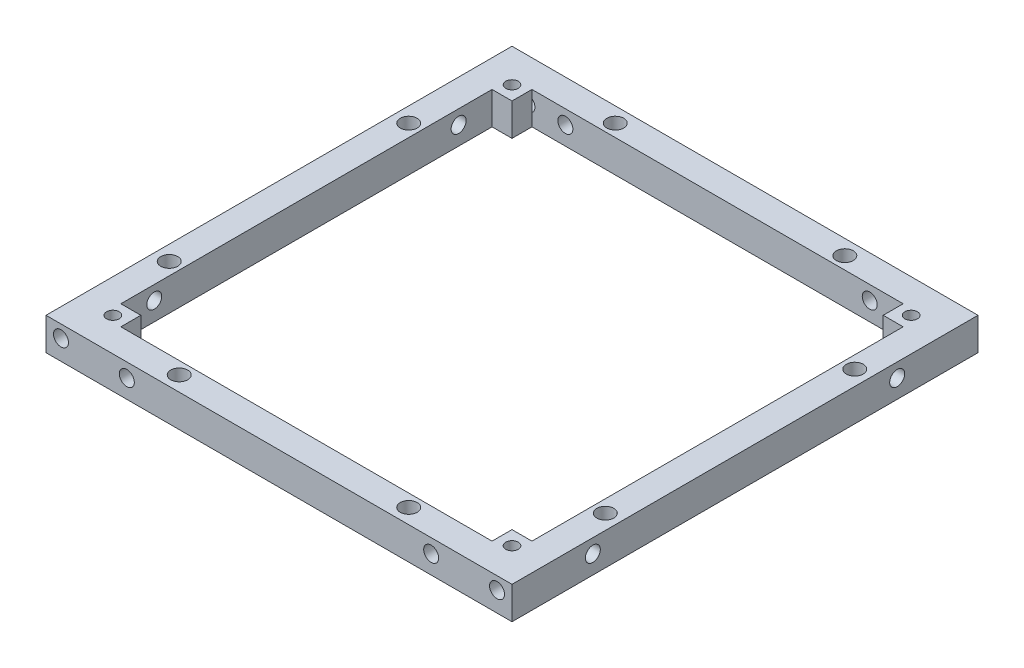
SolidWorks part; units mm, degrees
material "Aluminum"
ref_plane "Front Plane" through (0, 0, 0) normal (0, 0, 1) x (1, 0, 0)
ref_plane "Top Plane" through (0, 0, 0) normal (0, 1, 0) x (1, 0, 0)
ref_plane "Right Plane" through (0, 0, 0) normal (1, 0, 0) x (0, 0, -1)
sketch "Sketch1" plane through (0, 0, 0) normal (0, 1, 0) x (1, 0, 0)
  line L1 (46.7, -46.7) -> (-46.7, -46.7)
  line L2 (46.7, -46.7) -> (46.7, 46.7)
  line L3 (46.7, 46.7) -> (-46.7, 46.7)
  line L4 (-46.7, -46.7) -> (-46.7, 46.7)
  line L5 (46.7, -46.7) -> (-46.7, 46.7) construction
  line L6 (46.7, 46.7) -> (-46.7, -46.7) construction
  line L7 (38.7, -38.7) -> (-38.7, -38.7)
  line L8 (38.7, -38.7) -> (38.7, 38.7)
  line L9 (38.7, 38.7) -> (-38.7, 38.7)
  line L10 (-38.7, -38.7) -> (-38.7, 38.7)
  line L11 (38.7, -38.7) -> (-38.7, 38.7) construction
  line L12 (38.7, 38.7) -> (-38.7, -38.7) construction
  point P0 (0, 0)
  point P6 (0, 0)
  dimension "D1" = 93.4
  dimension "D2" = 93.4
  dimension "D3" = 8
extrude "Boss-Extrude1" add sketch "Sketch1" along normal blind 8
hole_wizard "Ø3.0 (3) Diameter Hole6" positions "Sketch8" profile "Sketch7" hole size "Ø3.0" standard "ANSI Metric"
sketch "Sketch8" plane through (0, 0, 46.7) normal (0, 0, 1) x (1, 0, 0)
  line L0 (46.7, 8) -> (46.7, 0) construction
  line L1 (-46.7, 8) -> (-46.7, 0) construction
  line L2 (-46.7, 0) -> (46.7, 0) construction
  point P0 (43.7, 4)
  point P2 (-43.7, 4)
  dimension "D1" = 3
  dimension "D2" = 3
  dimension "D3" = 4
  dimension "D4" = 4
sketch "Sketch7" plane through (43.7, 4, 46.7) normal (1, 0, 0) x (0, -1, 0)
  line L0 (0, 0) -> (0, 7.5)
  line L1 (0, 7.5) -> (1.5, 7.5)
  line L2 (1.5, 7.5) -> (1.5, 0)
  line L5 (1.5, 0) -> (0, 0)
  line L10 (0, 7.5) -> (-1.5, 7.5) construction
  line L11 (0, -6.35) -> (0, 107.95) construction
  dimension "Hole Dia." = 3
  dimension "Hole Depth" = 7.5
  dimension "Drill Angle" = 180
hole_wizard "Ø3.0 (3) Diameter Hole3" positions "Sketch10" profile "Sketch9" hole size "Ø3.0" standard "ANSI Metric"
sketch "Sketch10" plane through (0, 0, -46.7) normal (0, 0, -1) x (-1, 0, 0)
  line L0 (-46.7, 8) -> (-46.7, 0) construction
  line L1 (46.7, 8) -> (46.7, 0) construction
  line L2 (-46.7, 0) -> (46.7, 0) construction
  point P0 (-43.7, 4)
  point P2 (43.7, 4)
  dimension "D1" = 3
  dimension "D2" = 3
  dimension "D3" = 4
  dimension "D4" = 4
sketch "Sketch9" plane through (43.7, 4, -46.7) normal (1, 0, 0) x (0, 1, 0)
  line L0 (0, 0) -> (0, 7.5)
  line L1 (0, 7.5) -> (1.5, 7.5)
  line L2 (1.5, 7.5) -> (1.5, 0)
  line L5 (1.5, 0) -> (0, 0)
  line L10 (0, 7.5) -> (-1.5, 7.5) construction
  line L11 (0, -6.35) -> (0, 107.95) construction
  dimension "Hole Dia." = 3
  dimension "Hole Depth" = 7.5
  dimension "Drill Angle" = 180
sketch "Sketch27" plane through (0, 8, 0) normal (0, 1, 0) x (1, 0, 0)
  line L0 (-38.7, 38.7) -> (-38.7, -38.7) construction
  line L1 (39.7, -39.7) -> (-39.7, -39.7)
  line L2 (39.7, -39.7) -> (39.7, 39.7)
  line L3 (39.7, 39.7) -> (-39.7, 39.7)
  line L4 (-39.7, -39.7) -> (-39.7, 39.7)
  line L5 (39.7, -39.7) -> (-39.7, 39.7) construction
  line L6 (39.7, 39.7) -> (-39.7, -39.7) construction
  line L7 (38.7, 38.7) -> (-38.7, 38.7) construction
  point P0 (0, 0)
  dimension "D1" = 1
  dimension "D2" = 1
extrude "Cut-Extrude2" cut sketch "Sketch27" against normal blind 10
hole_wizard "Ø3.4 (3.4) Diameter Hole1" positions "Sketch37" profile "Sketch36" hole size "Ø3.4" standard "ANSI Metric" end condition through all
sketch "Sketch37" plane through (0, 0, 0) normal (0, -1, 0) x (-1, 0, 0)
  line L0 (39.7, -39.7) -> (-39.7, -39.7) construction
  line L1 (39.7, 39.7) -> (39.7, -39.7) construction
  line L2 (-39.7, -39.7) -> (-39.7, 39.7) construction
  line L3 (-39.7, 39.7) -> (39.7, 39.7) construction
  point P0 (-23, 43.7)
  point P2 (23, 43.7)
  point P4 (43.7, 23)
  point P6 (43.7, -25)
  point P8 (23, -43.7)
  point P10 (-23, -43.7)
  point P12 (-43.7, -25)
  point P14 (-43.7, 25)
  dimension "D1" = 46
  dimension "D2" = 4
  dimension "D3" = 48
  dimension "D4" = 50
  dimension "D5" = 46
  dimension "D6" = 4
  dimension "D7" = 4
  dimension "D8" = 4
sketch "Sketch36" plane through (23, 0, -43.7) normal (1, 0, 0) x (0, 0, -1)
  line L0 (0, 0) -> (0, 8)
  line L1 (0, 8) -> (1.7, 8)
  line L2 (1.7, 8) -> (1.7, 0)
  line L5 (1.7, 0) -> (0, 0)
  line L11 (0, -6.35) -> (0, 107.95) construction
  dimension "Thru Hole Dia." = 3.4
  dimension "Thru Hole Depth" = 8
sketch "Sketch38" plane through (0, 8, 0) normal (0, 1, 0) x (1, 0, 0)
  line L0 (46.7, 46.7) -> (-46.7, 46.7) construction
  line L1 (41.2, -41.2) -> (-41.2, -41.2)
  line L2 (41.2, -41.2) -> (41.2, 41.2)
  line L3 (41.2, 41.2) -> (-41.2, 41.2)
  line L4 (-41.2, -41.2) -> (-41.2, 41.2)
  line L5 (41.2, -41.2) -> (-41.2, 41.2) construction
  line L6 (41.2, 41.2) -> (-41.2, -41.2) construction
  line L7 (-46.7, 46.7) -> (-46.7, -46.7) construction
  point P0 (0, 0)
  dimension "D1" = 5.5
  dimension "D2" = 5.5
extrude "Cut-Extrude4" cut sketch "Sketch38" against normal blind 10
sketch "Sketch44" plane through (0, 0, 0) normal (0, -1, 0) x (1, 0, 0)
  line L0 (41.2, -41.2) -> (-41.2, -41.2) construction
  line L1 (41.2, -41.2) -> (37.2, -41.2)
  line L2 (41.2, -41.2) -> (41.2, -37.2)
  line L3 (41.2, -37.2) -> (37.2, -37.2)
  line L4 (37.2, -41.2) -> (37.2, -37.2)
  line L5 (41.2, 41.2) -> (41.2, -41.2) construction
  line L6 (0, 0) -> (0, -67.1068) construction
  line L7 (0, 0) -> (66.4168, 0) construction
  line L8 (-37.2, -41.2) -> (-37.2, -37.2)
  line L9 (-41.2, -37.2) -> (-37.2, -37.2)
  line L10 (-41.2, -41.2) -> (-41.2, -37.2)
  line L11 (-41.2, -41.2) -> (-37.2, -41.2)
  line L12 (-41.2, 41.2) -> (-37.2, 41.2)
  line L13 (-41.2, 41.2) -> (-41.2, 37.2)
  line L14 (-41.2, 37.2) -> (-37.2, 37.2)
  line L15 (-37.2, 41.2) -> (-37.2, 37.2)
  line L16 (37.2, 41.2) -> (37.2, 37.2)
  line L17 (41.2, 37.2) -> (37.2, 37.2)
  line L18 (41.2, 41.2) -> (41.2, 37.2)
  line L19 (41.2, 41.2) -> (37.2, 41.2)
  dimension "D1" = 4
  dimension "D2" = 4
extrude "Boss-Extrude2" add sketch "Sketch44" against normal blind 8
sketch "Sketch45" plane through (0, 8, 0) normal (0, 1, 0) x (1, 0, 0)
  line L1 (-42.5, 38.5) -> (-38.5, 38.5)
  line L2 (-42.5, 38.5) -> (-42.5, 35)
  line L3 (-42.5, 35) -> (-38.5, 35)
  line L4 (-38.5, 38.5) -> (-38.5, 35)
  dimension "D1" = 4
  dimension "D2" = 3.5
extrude "Boss-Extrude3" [suppressed] add sketch "Sketch45" against normal blind 8
hole_wizard "Tap Drill for M3x0.5 Tap1" positions "Sketch48" profile "Sketch46" hole size "M3x0.5" standard "ANSI Metric" end condition through all
sketch "Sketch48" plane through (0, 8, 0) normal (0, 1, 0) x (1, 0, 0)
  line L0 (0, 0) -> (0, -55.577) construction
  line L2 (0, 0) -> (77.8896, 0) construction
  point P0 (40, 40)
  point P2 (40, -40)
  point P4 (-40, -40)
  point P6 (-40, 40)
  point P18 (1.6745, 6.9664)
  dimension "D1" = 80
  dimension "D2" = 40
  dimension "D3" = 80
  dimension "D4" = 40
  dimension "D5" = 80
  dimension "D6" = 80
  dimension "D7" = 40
sketch "Sketch46" plane through (40, 8, -40) normal (1, 0, 0) x (0, 0, 1)
  line L0 (0, 0) -> (0, 8)
  line L1 (0, 8) -> (1.25, 8)
  line L2 (1.25, 8) -> (1.25, 0)
  line L5 (1.25, 0) -> (0, 0)
  line L11 (0, -6.35) -> (0, 107.95) construction
  dimension "Thru Hole Dia." = 2.5
  dimension "Thru Hole Depth" = 8
sketch "Sketch49" plane through (46.7, 0, 0) normal (1, 0, 0) x (0, 0, -1)
  line L0 (46.7, 8) -> (46.7, 0) construction
  line L1 (-46.7, 8) -> (46.7, 8)
  line L2 (-46.7, 8) -> (-46.7, 6.5)
  line L3 (-46.7, 6.5) -> (46.7, 6.5)
  line L4 (46.7, 8) -> (46.7, 6.5)
  dimension "D1" = 1.5
extrude "Cut-Extrude5" cut sketch "Sketch49" against normal blind 146
hole_wizard "Tap Drill for M3x0.5 Tap2" positions "Sketch51" profile "Sketch50" hole size "M3x0.5" standard "ANSI Metric" end condition up to next
sketch "Sketch51" plane through (-46.7, 0, 0) normal (-1, 0, 0) x (0, 0, 1)
  point P0 (30.5, 3.7)
  point P3 (-30.5, 3.7)
sketch "Sketch50" plane through (-46.7, 3.7, 30.5) normal (0, 1, 0) x (0, 0, 1)
  line L0 (0, 0) -> (0, 5.5)
  line L1 (0, 5.5) -> (1.5, 5.5)
  line L2 (1.5, 5.5) -> (1.5, 0)
  line L5 (1.5, 0) -> (0, 0)
  line L11 (0, -6.35) -> (0, 107.95) construction
  dimension "Thru Hole Dia." = 3
  dimension "Thru Hole Depth" = 5.5
hole_wizard "Tap Drill for M3x0.5 Tap3" positions "Sketch53" profile "Sketch52" hole size "M3x0.5" standard "ANSI Metric" end condition up to next
sketch "Sketch53" plane through (0, 0, -46.7) normal (0, 0, -1) x (-1, 0, 0)
  point P0 (30.5, 3.7)
  point P3 (-30.5, 3.7)
sketch "Sketch52" plane through (-30.5, 3.7, -46.7) normal (1, 0, 0) x (0, 1, 0)
  line L0 (0, 0) -> (0, 5.5)
  line L1 (0, 5.5) -> (1.5, 5.5)
  line L2 (1.5, 5.5) -> (1.5, 0)
  line L5 (1.5, 0) -> (0, 0)
  line L11 (0, -6.35) -> (0, 107.95) construction
  dimension "Thru Hole Dia." = 3
  dimension "Thru Hole Depth" = 5.5
hole_wizard "Tap Drill for M3x0.5 Tap4" positions "Sketch55" profile "Sketch54" hole size "M3x0.5" standard "ANSI Metric" end condition up to next
sketch "Sketch55" plane through (46.7, 0, 0) normal (1, 0, 0) x (0, 0, -1)
  point P0 (30.5, 3.7)
  point P3 (-30.5, 3.7)
sketch "Sketch54" plane through (46.7, 3.7, -30.5) normal (0, 1, 0) x (0, 0, -1)
  line L0 (0, 0) -> (0, 5.5)
  line L1 (0, 5.5) -> (1.5, 5.5)
  line L2 (1.5, 5.5) -> (1.5, 0)
  line L5 (1.5, 0) -> (0, 0)
  line L11 (0, -6.35) -> (0, 107.95) construction
  dimension "Thru Hole Dia." = 3
  dimension "Thru Hole Depth" = 5.5
hole_wizard "Tap Drill for M3x0.5 Tap5" positions "Sketch57" profile "Sketch56" hole size "M3x0.5" standard "ANSI Metric" end condition up to next
sketch "Sketch57" plane through (0, 0, 46.7) normal (0, 0, 1) x (1, 0, 0)
  point P0 (30.5, 3.7)
  point P3 (-30.5, 3.7)
sketch "Sketch56" plane through (30.5, 3.7, 46.7) normal (1, 0, 0) x (0, -1, 0)
  line L0 (0, 0) -> (0, 5.5)
  line L1 (0, 5.5) -> (1.5, 5.5)
  line L2 (1.5, 5.5) -> (1.5, 0)
  line L5 (1.5, 0) -> (0, 0)
  line L11 (0, -6.35) -> (0, 107.95) construction
  dimension "Thru Hole Dia." = 3
  dimension "Thru Hole Depth" = 5.5
hole_wizard "Tap Drill for M3x0.5 Tap6" positions "Sketch59" profile "Sketch58" hole size "M3x0.5" standard "ANSI Metric"
sketch "Sketch59" plane through (0, 0, -46.7) normal (0, 0, -1) x (-1, 0, 0)
  line L0 (0, 0) -> (0, -19.6512) construction
  point P0 (38.1, 3.7)
  point P2 (-38.1, 3.7)
  dimension "D1" = 38.1
  dimension "D2" = 38.1
sketch "Sketch58" plane through (-38.1, 3.7, -46.7) normal (1, 0, 0) x (0, 1, 0)
  line L0 (0, 0) -> (0, 5.5)
  line L1 (0, 5.5) -> (1.5, 5.5)
  line L2 (1.5, 5.5) -> (1.5, 0)
  line L5 (1.5, 0) -> (0, 0)
  line L10 (0, 5.5) -> (-1.5, 5.5) construction
  line L11 (0, -6.35) -> (0, 107.95) construction
  dimension "Hole Dia." = 3
  dimension "Hole Depth" = 5.5
  dimension "Drill Angle" = 180
